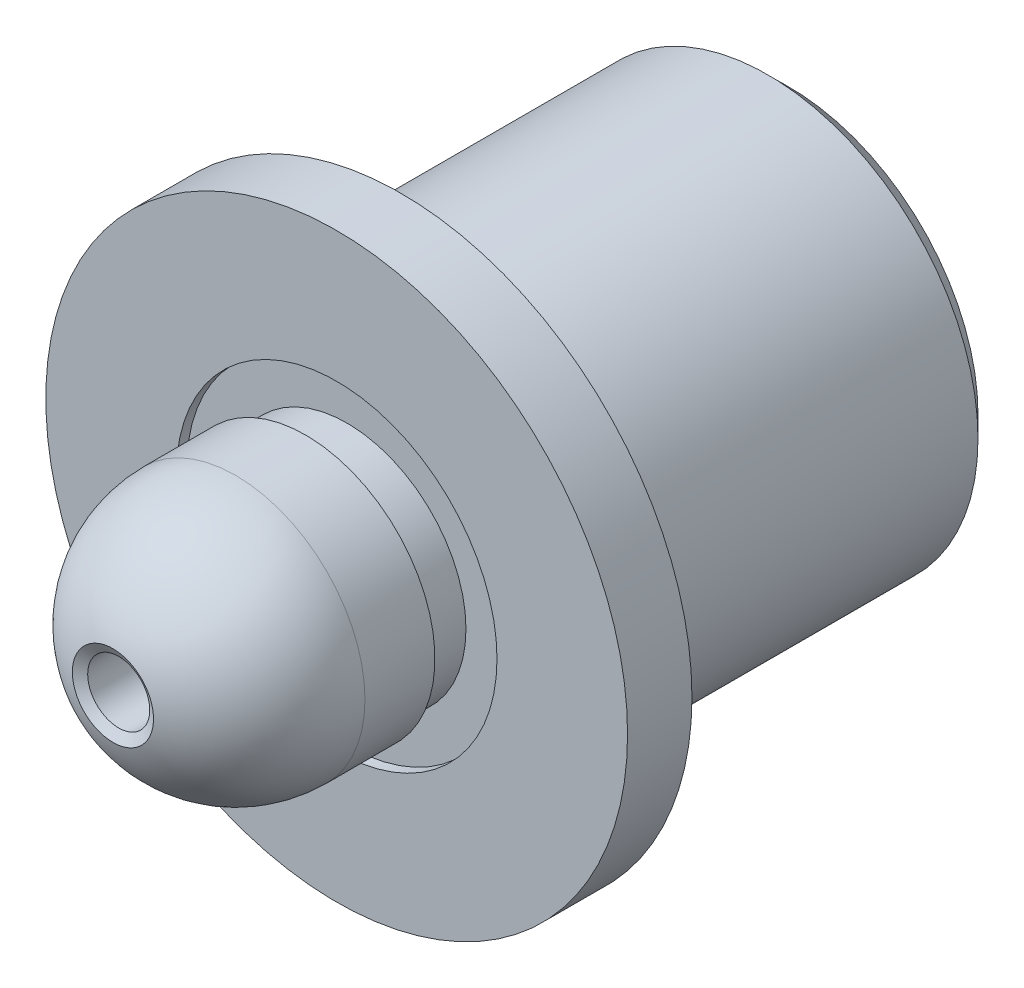
SolidWorks part; units mm, degrees
ref_plane "Front" through (0, 0, 0) normal (0, 0, 1) x (1, 0, 0)
ref_plane "Top" through (0, 0, 0) normal (0, 1, 0) x (1, 0, 0)
ref_plane "Right" through (0, 0, 0) normal (1, 0, 0) x (0, 0, -1)
sketch "Sketch1" plane through (0, 0, 0) normal (1, 0, 0) x (0, 0, -1)
  line L0 (0, 0) -> (-16.6687, 0) construction
  line L1 (0, 0) -> (37.8366, 0) construction
  line L2 (0, 0) -> (0, -30.2693) construction
  line L3 (0, 0) -> (0, 5.1594)
  line L4 (0, 5.1594) -> (-9.525, 5.1594)
  line L5 (-9.525, 5.1594) -> (-9.525, 7.1438)
  line L6 (-9.525, 7.1438) -> (-11.1061, 7.1437)
  line L7 (-11.1061, 7.1437) -> (-11.1061, 3.175)
  line L8 (-11.1061, 3.175) -> (-13.5865, 3.175)
  line L9 (-16.6687, 0) -> (-16.6687, -15.5339) construction
  line L10 (-8.3808, 0) -> (-8.3808, -24.0717) construction
  line L11 (-9.779, 5.9214) -> (-9.525, 5.9214) construction
  line L12 (-11.1061, 3.937) -> (-10.8521, 3.937) construction
  line L13 (-11.8681, 3.175) -> (-11.8681, 2.921) construction
  line L14 (-11.8681, 2.921) -> (-10.8521, 2.921) construction
  line L15 (-10.8521, 3.937) -> (-10.8521, 2.921) construction
  line L16 (-16.6687, 0) -> (-16.6687, 0.762) construction
  line L17 (-16.6687, 0) -> (-16.7615, 0) construction
  line L18 (-16.7615, 0) -> (-16.7615, -0.6279) construction
  line L19 (-8.763, 5.1594) -> (-8.763, 4.9054) construction
  line L20 (-8.763, 4.9054) -> (-9.779, 4.9054) construction
  line L21 (-9.779, 5.9214) -> (-9.779, 4.9054) construction
  line L22 (-16.7615, 0) -> (0, 0)
  arc A0 (-13.5865, 3.175) -> (-16.7615, 0) centre (-13.5865, 0) ccw
  dimension "D" = 16.6687
  dimension "B" = 10.3187
  dimension "C" = 5.5626
  dimension "E" = 9.525
  dimension "A" = 6.35
  dimension "F" = 14.2875
  dimension "D7" = 0.254
  dimension "D8" = 1.016
  dimension "D1" = 1.524
ref_axis "Axis1" through (0, 0, 17.4309) along (0, 0, -1)
revolve "Revolve1" add sketch "Sketch1" angle 360 about axis through (0, 0, 17.4309) along (0, 0, -1)
sketch "Sketch3" plane through (0, 0, 0) normal (1, 0, 0) x (0, 0, -1)
  line L1 (-11.8681, 2.921) -> (-10.8521, 2.921)
  line L2 (-11.8681, 2.921) -> (-11.8681, 3.937)
  line L3 (-11.8681, 3.937) -> (-10.8521, 3.937)
  line L4 (-10.8521, 2.921) -> (-10.8521, 3.937)
  line L5 (-9.779, 5.9214) -> (-8.763, 5.9214)
  line L6 (-9.779, 5.9214) -> (-9.779, 4.9054)
  line L7 (-9.779, 4.9054) -> (-8.763, 4.9054)
  line L8 (-8.763, 5.9214) -> (-8.763, 4.9054)
revolve "Cut-Revolve1" cut sketch "Sketch3" angle 360 about axis through (0, 0, 17.4309) along (0, 0, -1)
chamfer "Chamfer1" distance 0.5159 angle 45 1 edges at (5.1594, 0, 0)
sketch "Sketch2" plane through (0, 0, 0) normal (0, 0, -1) x (-1, 0, 0)
  circle A0 centre (0, 0) radius 0.762
  dimension "D1" = 1.524
extrude "Cut-Extrude1" cut sketch "Sketch2" against normal blind 2.54
ref_plane "Plane1" through (0, 0, 8.3808) normal (0, 0, 1) x (1, 0, 0)
mirror "Mirror1" about plane through (0, 0, 8.3808) normal (0, 0, 1) of "Cut-Extrude1"
chamfer "Chamfer2" distance 0.254 angle 45 2 edges at (-0.762, 0, 0) (-0.762, 0, 16.6687) first distance on face at (-0.762, 0, 0) first distance on face at (3.175, 0, 13.5865)
equation "\"D1@Chamfer1\" = \"B@Sketch1\"*.05"
